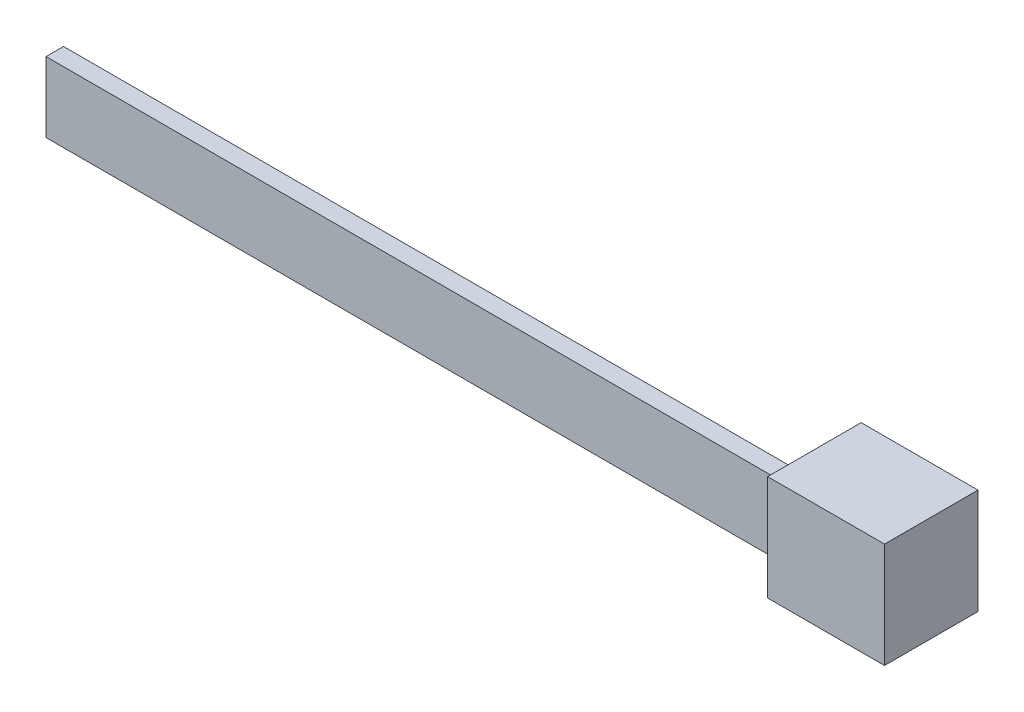
SolidWorks part; units mm, degrees
ref_plane "Front Plane" through (0, 0, 0) normal (0, 0, 1) x (1, 0, 0)
ref_plane "Top Plane" through (0, 0, 0) normal (0, 1, 0) x (1, 0, 0)
ref_plane "Right Plane" through (0, 0, 0) normal (1, 0, 0) x (0, 0, -1)
sketch "Sketch1" plane through (0, 0, 0) normal (0, 1, 0) x (1, 0, 0)
  line L1 (0, -4) -> (10, -4)
  line L2 (0, -4) -> (0, 4)
  line L3 (0, 4) -> (10, 4)
  line L4 (10, -4) -> (10, 4)
  line L5 (0, 0.75) -> (-65, 0.75)
  line L6 (0, 0.75) -> (0, -0.75)
  line L7 (0, -0.75) -> (-65, -0.75)
  line L8 (-65, 0.75) -> (-65, -0.75)
  line L9 (-32.5, -0.75) -> (-32.5, 0.75) construction
  line L10 (0, 0) -> (-65, 0) construction
  point P85 (-32.5, 0)
  dimension "D1" = 75
  dimension "D2" = 1.5
  dimension "D3" = 8
  dimension "D4" = 10
extrude "Boss-Extrude1" add sketch "Sketch1" along normal mid plane 6 contours L5 L8 L7 L2 | L1 L4 L3 L2 region at (5, 0, 0) region at (-32.5, 0, 0)
sketch "Sketch2" plane through (0, 3, 0) normal (0, 1, 0) x (1, 0, 0)
  line L1 (0, 4) -> (10, 4)
  line L2 (0, 4) -> (0, -4)
  line L3 (0, -4) -> (10, -4)
  line L4 (10, 4) -> (10, -4)
  line L5 (5, -4) -> (5, 4) construction
  line L6 (0, 0) -> (10, 0) construction
  point P108 (5, 0)
extrude "Boss-Extrude2" add sketch "Sketch2" along normal blind 3
